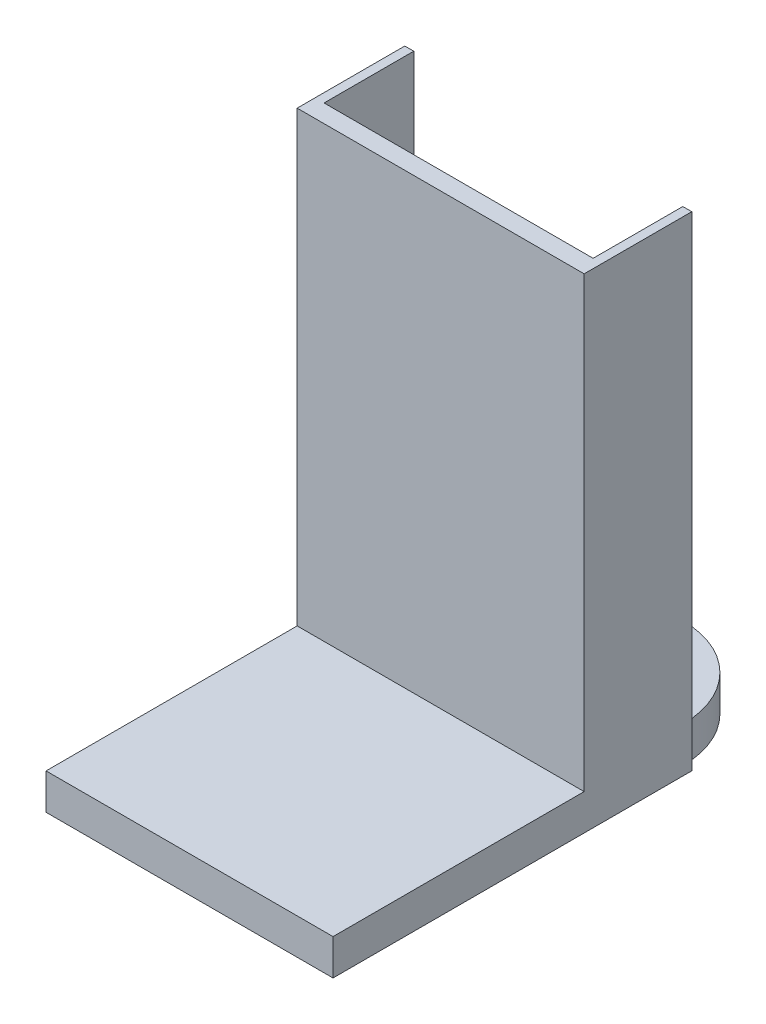
SolidWorks part; units mm, degrees
ref_plane "Front Plane" through (0, 0, 0) normal (0, 0, 1) x (1, 0, 0)
ref_plane "Top Plane" through (0, 0, 0) normal (0, 1, 0) x (1, 0, 0)
ref_plane "Right Plane" through (0, 0, 0) normal (1, 0, 0) x (0, 0, -1)
sketch "Sketch2" plane through (0, 0, 0) normal (0, 1, 0) x (1, 0, 0)
  line L0 (155, 200) -> (160, 200)
  line L1 (0, 0) -> (160, 0)
  line L2 (0, 0) -> (0, 200)
  line L3 (0, 200) -> (5, 200)
  line L4 (160, 0) -> (160, 200)
  line L6 (5, 200) -> (5, 250)
  line L7 (5, 250) -> (155, 250)
  line L8 (155, 200) -> (155, 250)
  dimension "D1" = 160
  dimension "D2" = 200
  dimension "D3" = 5
  dimension "D4" = 5
  dimension "D5" = 50
extrude "Boss-Extrude1" add sketch "Sketch2" along normal blind 20
fillet "Fillet1" radius 50 2 edges at (155, 10, -250) (5, 10, -250)
sketch "Sketch3" plane through (0, 20, 0) normal (0, 1, 0) x (1, 0, 0)
  line L0 (0, 200) -> (0, 140)
  line L1 (0, 200) -> (0, 0) construction
  line L2 (0, 140) -> (160, 140)
  line L3 (160, 0) -> (160, 200) construction
  line L4 (160, 140) -> (160, 200)
  line L5 (160, 200) -> (155, 200)
  line L6 (5, 200) -> (0, 200) construction
  line L7 (155, 200) -> (155, 150)
  line L8 (155, 150) -> (5, 150)
  line L9 (5, 150) -> (5, 200)
  line L10 (5, 200) -> (0, 200)
  dimension "D1" = 5
  dimension "D2" = 5
  dimension "D3" = 50
  dimension "D4" = 10
extrude "Boss-Extrude2" add sketch "Sketch3" along normal blind 250
